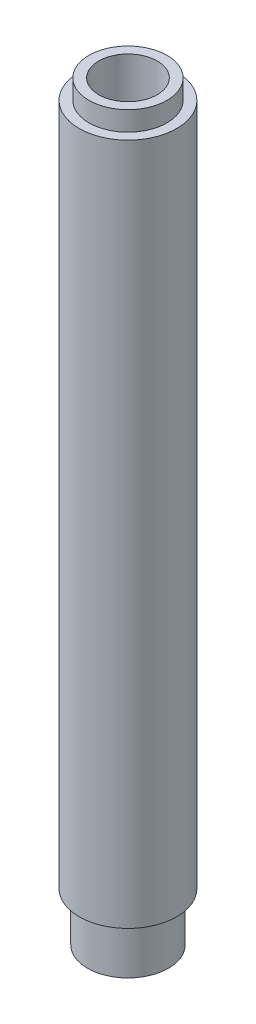
SolidWorks part; units mm, degrees
ref_plane "Front Plane" through (0, 0, 0) normal (0, 0, 1) x (1, 0, 0)
ref_plane "Top Plane" through (0, 0, 0) normal (0, 1, 0) x (1, 0, 0)
ref_plane "Right Plane" through (0, 0, 0) normal (1, 0, 0) x (0, 0, -1)
sketch "Sketch1" plane through (0, 0, 0) normal (0, 1, 0) x (1, 0, 0)
  circle A0 centre (0, 0) radius 12.7
  dimension "D1" = 25.4
extrude "Boss-Extrude1" add sketch "Sketch1" along normal blind 177.8
sketch "Sketch4" plane through (0, 177.8, 0) normal (0, 1, 0) x (1, 0, 0)
  circle A2 centre (0, 0) radius 10.16
  circle A3 centre (0, 0) radius 10.16
  dimension "D1" = 2.54
extrude "Boss-Extrude2" add sketch "Sketch4" along normal blind 5.08
sketch "Sketch5" plane through (0, 182.88, 0) normal (0, 1, 0) x (1, 0, 0)
  circle A0 centre (0, 0) radius 10.16 construction
  circle A1 centre (0, 0) radius 10.16 construction
  circle A2 centre (0, 0) radius 7.62
  dimension "D1" = 2.54
extrude "Cut-Extrude1" cut sketch "Sketch5" against normal through all
sketch "Sketch6" plane through (0, 0, 0) normal (0, -1, 0) x (1, 0, 0)
  circle A0 centre (0, 0) radius 10.541
  circle A1 centre (0, 0) radius 7.62 construction
  circle A2 centre (0, 0) radius 7.62
  dimension "D1" = 21.082
extrude "Boss-Extrude3" add sketch "Sketch6" along normal blind 12.7
sketch "Sketch7" plane through (0, -12.7, 0) normal (0, -1, 0) x (1, 0, 0)
  circle A0 centre (0, 0) radius 12.7 construction
  circle A1 centre (0, 0) radius 12.7
sketch "Sketch8" plane through (0, 182.88, 0) normal (0, 1, 0) x (1, 0, 0)
  circle A0 centre (0, 0) radius 12.7 construction
  circle A1 centre (0, 0) radius 12.7
